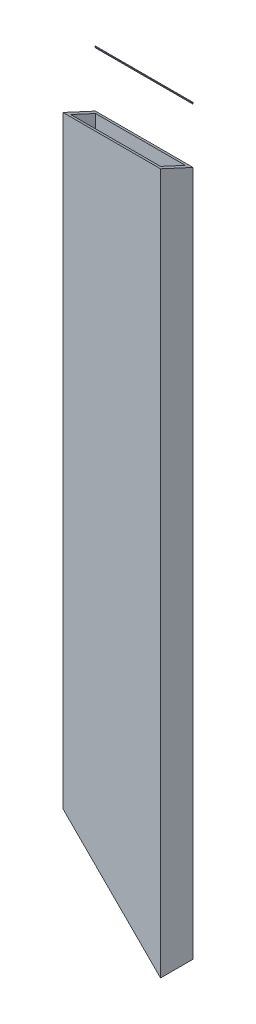
SolidWorks part; units mm, degrees
note: '?' marks a value the reader was unsure of.
material "A500"
ref_plane "Front Plane" through (0, 0, 0) normal (0, 0, 1) x (1, 0, 0)
ref_plane "Top Plane" through (0, 0, 0) normal (0, 1, 0) x (1, 0, 0)
ref_plane "Right Plane" through (0, 0, 0) normal (1, 0, 0) x (0, 0, -1)
sketch "Sketch1" plane through (0, 0, 0) normal (0, 1, 0) x (1, 0, 0)
  line L0 (0, 9.652) -> (0, 12.7) construction
  line L1 (-38.1, 12.7) -> (38.1, 12.7)
  line L2 (-38.1, 12.7) -> (-38.1, -12.7)
  line L3 (-38.1, -12.7) -> (38.1, -12.7)
  line L4 (38.1, 12.7) -> (38.1, -12.7)
  line L5 (-35.052, 9.652) -> (35.052, 9.652)
  line L6 (-35.052, 9.652) -> (-35.052, -9.652)
  line L7 (-35.052, -9.652) -> (35.052, -9.652)
  line L8 (35.052, 9.652) -> (35.052, -9.652)
  line L9 (35.052, 0) -> (38.1, 0) construction
  line L10 (0, -9.652) -> (0, -12.7) construction
  line L11 (-35.052, 0) -> (-38.1, 0) construction
  line L12 (0, 9.652) -> (0, 0) construction
  line L13 (0, 0) -> (-35.052, 0) construction
  dimension "D1" = 76.2
  dimension "D2" = 25.4
  dimension "D3" = 3.048
extrude "Boss-Extrude1" add sketch "Sketch1" along normal up to vertex (503 mm away)
ref_plane "Plane1" through (0, 0, 0) normal (0, 0, 1) x (1, 0, 0)
sketch "Sketch2" plane through (0, 0, 0) normal (0, 0, 1) x (1, 0, 0)
  line L0 (0, 0) -> (0, 503) construction
  line L1 (-38.1, 503) -> (38.1, 503) construction
  line L2 (0, 251.5) -> (-38.1, 251.5) construction
  line L3 (-38.1, 503) -> (-38.1, 0) construction
  line L4 (0, 251.5) -> (38.1, 251.5) construction
  line L5 (38.1, 503) -> (38.1, 0) construction
ref_axis "Axis1" through (0, 503, 0) along (0, -1, 0)?
sketch "Sketch3" plane through (0, 0, 0) normal (0, -1, 0) x (1, 0, 0)
  line L0 (-35.052, -9.652) -> (-35.052, 9.652) construction
  line L1 (-35.052, 9.652) -> (35.052, 9.652) construction
  line L2 (35.052, -9.652) -> (-35.052, -9.652) construction
  line L3 (35.052, 9.652) -> (35.052, -9.652) construction
  line L4 (-38.1, 12.7) -> (-38.1, -12.7)
  line L5 (-38.1, -12.7) -> (38.1, -12.7)
  line L6 (38.1, -12.7) -> (38.1, 12.7)
  line L7 (38.1, 12.7) -> (-38.1, 12.7)
  line L8 (-38.1, 12.7) -> (-38.1, -12.7)
  line L9 (-38.1, -12.7) -> (38.1, -12.7)
  line L10 (38.1, -12.7) -> (38.1, 12.7)
  line L11 (38.1, 12.7) -> (-38.1, 12.7)
  line L12 (-35.052, -9.652) -> (-35.052, 9.652)
  line L13 (-35.052, 9.652) -> (35.052, 9.652)
  line L14 (35.052, -9.652) -> (-35.052, -9.652)
  line L15 (35.052, 9.652) -> (35.052, -9.652)
  dimension "D1" = 0
extrude "Boss-Extrude2" add sketch "Sketch3" along normal blind 38.1
sketch "Sketch4" plane through (0, 503, 0) normal (0, 1, 0) x (1, 0, 0)
  line L0 (-35.052, 9.652) -> (-35.052, -9.652) construction
  line L1 (-35.052, -9.652) -> (35.052, -9.652) construction
  line L2 (35.052, 9.652) -> (-35.052, 9.652) construction
  line L3 (35.052, -9.652) -> (35.052, 9.652) construction
  line L4 (-38.1, 12.7) -> (-38.1, -12.7)
  line L5 (-38.1, -12.7) -> (38.1, -12.7)
  line L6 (38.1, -12.7) -> (38.1, 12.7)
  line L7 (38.1, 12.7) -> (-38.1, 12.7)
  line L8 (-38.1, 12.7) -> (-38.1, -12.7)
  line L9 (-38.1, -12.7) -> (38.1, -12.7)
  line L10 (38.1, -12.7) -> (38.1, 12.7)
  line L11 (38.1, 12.7) -> (-38.1, 12.7)
  line L12 (-35.052, 9.652) -> (-35.052, -9.652)
  line L13 (-35.052, -9.652) -> (35.052, -9.652)
  line L14 (35.052, 9.652) -> (-35.052, 9.652)
  line L15 (35.052, -9.652) -> (35.052, 9.652)
  dimension "D1" = 0
extrude "Boss-Extrude3" add sketch "Sketch4" along normal blind 38.1
sketch "Sketch5" plane through (0, 0, 0) normal (0, 0, 1) x (1, 0, 0)
  line L0 (-63.7044, 63.8242) -> (106.5591, -106.632)
  line L1 (-63.7044, 63.8242) -> (0, 25.4) construction
  line L2 (0, 0) -> (0, 503) construction
  line L3 (-63.7044, 63.8242) -> (-25.4, 0.0477) construction
  line L4 (-500, 0.0477) -> (0, 0.0477) construction
  line L7 (-63.7044, 63.8242) -> (-66.4049, -106.632)
  line L8 (-66.4049, -106.632) -> (106.5591, -106.632)
  dimension "D1" = 25.4
  dimension "D2" = 25.4
extrude "Cut-Extrude1" cut sketch "Sketch5" against normal through all both and the other way through all
sketch "Sketch6" plane through (38.1, 0, 0) normal (1, 0, 0) x (0, 0, -1)
  line L0 (33.5184, 487.4506) -> (-43.414, 523.14)
  line L1 (0, 0) -> (0, 503) construction
  line L2 (0, 503) -> (152.7, 632.1616) construction
  line L3 (33.5184, 487.4506) -> (0, 474.1267) construction
  line L4 (33.5184, 487.4506) -> (22.0448, 521.6466) construction
  line L5 (0, 474.1267) -> (0, 503) construction
  line L6 (0, 503) -> (22.0448, 521.6466) construction
  line L8 (10.6349, 545.0176) -> (33.5184, 487.4506)
  line L9 (-43.414, 523.14) -> (0, 598.233)
  line L10 (0, 598.233) -> (10.6349, 545.0176)
  point P4 (0, 503)
extrude "Cut-Extrude2" cut sketch "Sketch6" against normal through all
equation "\"tubeMainWidth\"= 76.2mm"
equation "\"tubeSecondWidth\"= 25.4mm"
equation "\"tubeThickness\"= 3.048mm"
equation "\"halfMainWidthOfTubing\"= (\"tubeMainWidth\"/2)"
equation "\"D1@Sketch1\"=\"tubeMainWidth\""
equation "\"D2@Sketch1\"=\"tubeSecondWidth\""
equation "\"D3@Sketch1\"=\"tubeThickness\""
equation "\"D1@Boss-Extrude2\"=\"halfMainWidthOfTubing\""
equation "\"D1@Boss-Extrude3\"=\"halfMainWidthOfTubing\""
